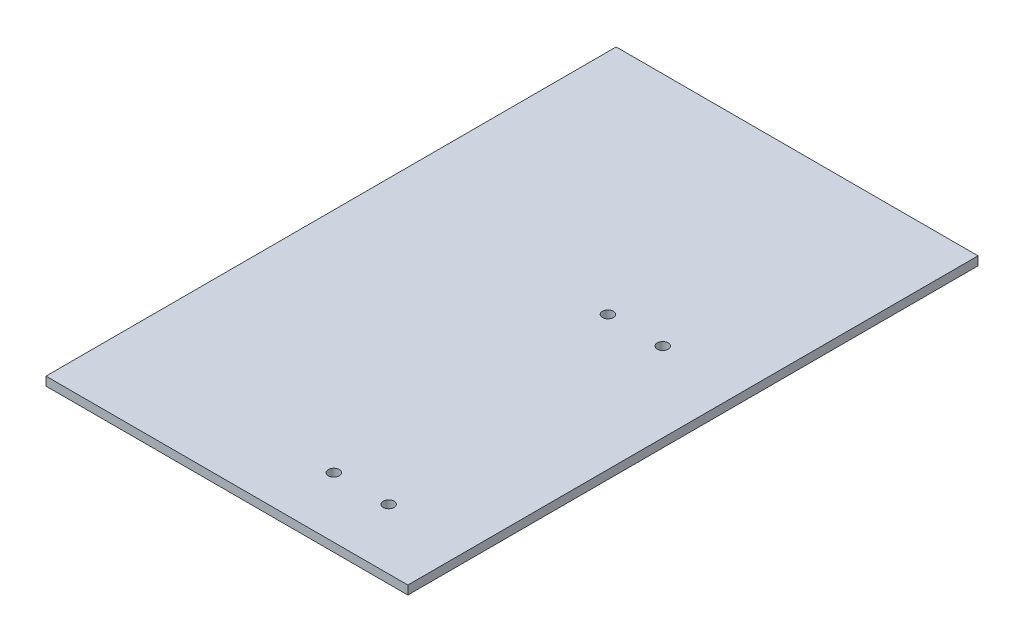
SolidWorks part; units mm, degrees
material "Alliage 1060"
ref_plane "Plan de face" through (0, 0, 0) normal (0, 0, 1) x (1, 0, 0)
ref_plane "Plan de dessus" through (0, 0, 0) normal (0, 1, 0) x (1, 0, 0)
ref_plane "Plan de droite" through (0, 0, 0) normal (1, 0, 0) x (0, 0, -1)
sketch "Esquisse1" plane through (0, 0, 0) normal (0, 1, 0) x (1, 0, 0)
  line L1 (-33, -52) -> (33, -52)
  line L2 (-33, -52) -> (-33, 52)
  line L3 (-33, 52) -> (33, 52)
  line L4 (33, -52) -> (33, 52)
  line L5 (-33, -52) -> (33, 52) construction
  line L6 (-33, 52) -> (33, -52) construction
  point P0 (0, 0)
  dimension "D1" = 104
  dimension "D2" = 66
extrude "Boss.-Extru.1" add sketch "Esquisse1" along normal blind 1.5875
sketch "Esquisse2" plane through (-33, 0, 0) normal (-1, 0, 0) x (0, 0, 1)
  line L1 (-52, 0) -> (52, 0)
  line L2 (-52, 0) -> (-52, 4)
  line L3 (-52, 4) -> (52, 4)
  line L4 (52, 0) -> (52, 4)
  dimension "D1" = 4
  dimension "D2" = 104
extrude "Boss.-Extru.2" [suppressed] add sketch "Esquisse2" along normal blind 1.5875 contours L3 L4 L1 L2
sketch "Esquisse3" plane through (33, 0, 0) normal (1, 0, 0) x (0, 0, -1)
  line L1 (-52, 0) -> (52, 0)
  line L2 (-52, 0) -> (-52, 4)
  line L3 (-52, 4) -> (52, 4)
  line L4 (52, 0) -> (52, 4)
  dimension "D1" = 104
  dimension "D2" = 4
extrude "Boss.-Extru.3" [suppressed] add sketch "Esquisse3" along normal blind 1.5875
fillet "Congé2" [suppressed] radius 2 type face fillet
fillet "Congé3" [suppressed] radius 2 type face fillet
sketch "Esquisse4" plane through (0, 1.5875, 0) normal (0, 1, 0) x (1, 0, 0)
  line L1 (18.5, -41) -> (8.5, -41) construction
  line L2 (18.5, -41) -> (18.5, 9) construction
  line L3 (18.5, 9) -> (8.5, 9) construction
  line L4 (8.5, -41) -> (8.5, 9) construction
  line L5 (33, -52) -> (33, 52) construction
  line L6 (-33, -52) -> (33, -52) construction
  line L8 (18.5, -41) -> (8.5, 9) construction
  line L9 (8.5, -41) -> (18.5, 9) construction
  circle A0 centre (8.5, 9) radius 1
  circle A1 centre (18.5, 9) radius 1
  circle A2 centre (18.5, -41) radius 1
  circle A3 centre (8.5, -41) radius 1
  dimension "D5" = 2
  dimension "D1" = 50
  dimension "D2" = 10
  dimension "D3" = 14.5
  dimension "D4" = 11
extrude "Enlèv. mat.-Extru.1" cut sketch "Esquisse4" against normal blind 1.5875 contours A0 | A1 | A3 | A2
